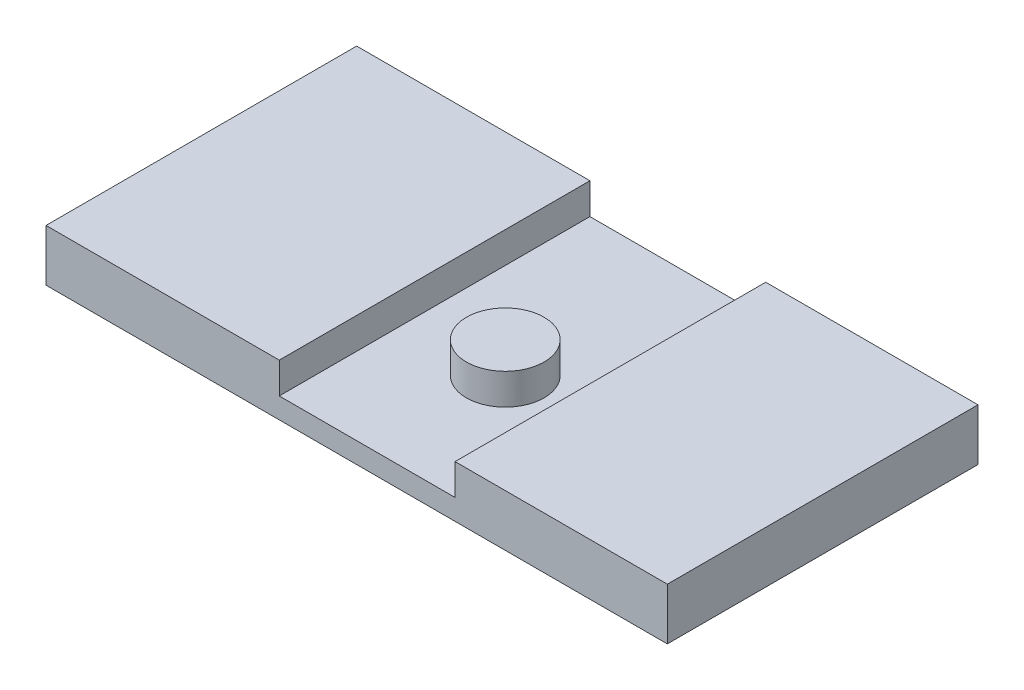
SolidWorks part; units mm, degrees
ref_plane "Front Plane" through (0, 0, 0) normal (0, 0, 1) x (1, 0, 0)
ref_plane "Top Plane" through (0, 0, 0) normal (0, 1, 0) x (1, 0, 0)
ref_plane "Right Plane" through (0, 0, 0) normal (1, 0, 0) x (0, 0, -1)
sketch "Sketch1" plane through (0, 0, 0) normal (0, 1, 0) x (1, 0, 0)
  line L1 (-152.4, -76.2) -> (152.4, -76.2)
  line L2 (-152.4, -76.2) -> (-152.4, 76.2)
  line L3 (-152.4, 76.2) -> (152.4, 76.2)
  line L4 (152.4, -76.2) -> (152.4, 76.2)
  line L5 (-152.4, -76.2) -> (152.4, 76.2) construction
  line L6 (-152.4, 76.2) -> (152.4, -76.2) construction
  point P0 (0, 0)
  dimension "D1" = 152.4
  dimension "D2" = 304.8
extrude "Boss-Extrude1" add sketch "Sketch1" along normal blind 25.4
sketch "Sketch2" plane through (0, 25.4, 0) normal (0, 1, 0) x (-1, 0, 0)
  line L0 (-152.4, -76.2) -> (152.4, -76.2) construction
  line L1 (37.973, -76.2) -> (-48.26, -76.2)
  line L2 (37.973, -76.2) -> (37.973, 76.2)
  line L3 (37.973, 76.2) -> (-48.26, 76.2)
  line L4 (-48.26, -76.2) -> (-48.26, 76.2)
  point P0 (0, 0)
  point P6 (-50.8, -76.2)
  dimension "D1" = 152.4
  dimension "D2" = 37.973
  dimension "D3" = 48.26
extrude "Cut-Extrude1" cut sketch "Sketch2" against normal blind 15.24
sketch "Sketch3" plane through (0, 10.16, 0) normal (0, 1, 0) x (-1, 0, 0)
  line L0 (37.973, 76.2) -> (-48.26, 76.2) construction
  circle A0 centre (-8.763, 12.065) radius 19.05
  dimension "D1" = 38.1
  dimension "D2" = 64.135
  dimension "D3" = 46.736
extrude "Boss-Extrude2" add sketch "Sketch3" along normal up to surface (15.24 mm away) up to face at (100.33, 25.4, 0)
sketch "Sketch4" plane through (0, 10.16, 0) normal (0, 1, 0) x (1, 0, 0)
  circle A0 centre (8.763, -12.065) radius 19.685
  circle A1 centre (8.763, -12.065) radius 19.05 construction
  dimension "D1" = 39.37
